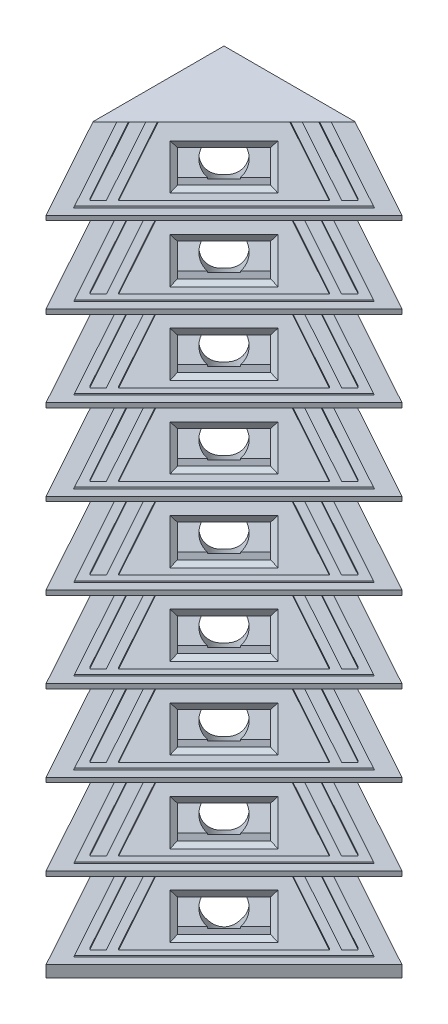
SolidWorks part; units mm, degrees
note: The reader was unsure of these and kept them because the rebuilt part matched: shared geometry of "Sketch6<6>", "Sketch6<8>", "Sketch6<10>".
ref_plane "Front Plane" through (0, 0, 0) normal (0, 0, 1) x (1, 0, 0)
ref_plane "Top Plane" through (0, 0, 0) normal (0, 1, 0) x (1, 0, 0)
ref_plane "Right Plane" through (0, 0, 0) normal (1, 0, 0) x (0, 0, -1)
sketch "Sketch1" plane through (0, 0, 0) normal (0, 1, 0) x (1, 0, 0)
  line L0 (0, 0) -> (0, -34)
  line L1 (0, -55) -> (0, 55) construction
  line L2 (0, -34) -> (34, 0)
  line L3 (-55, 0) -> (55, 0) construction
  line L4 (34, 0) -> (0, 0)
  dimension "D1" = 34
extrude "Boss-Extrude1" add sketch "Sketch1" along normal blind 143
sketch "Sketch3" plane through (17, 0, 17) normal (0.7071, 0, 0.7071) x (0.7071, 0, -0.7071)
  line L0 (-24.0416, 7.9909) -> (24.0416, 7.9909)
  line L1 (-24.0416, 143) -> (-24.0416, 0) construction
  line L2 (24.0416, 143) -> (24.0416, 0) construction
ref_plane "Plane2" through (15.1967, 12.4081, 15.1967) normal (0.6124, 0.5, 0.6124) x (0.7071, 0, -0.7071)
sketch "Sketch6" plane through (15.1967, 12.4081, 15.1967) normal (0.6124, 0.5, 0.6124) x (0.7071, 0, -0.7071)
  line L0 (-24.0416, -5.1005) -> (24.0416, -5.1005)
  line L1 (24.0416, -5.1005) -> (24.0416, 7.5577)
  line L2 (24.0416, 7.5577) -> (-24.0416, 7.5577)
  line L3 (-24.0416, 7.5577) -> (-24.0416, -5.1005)
  line L4 (0, 7.5577) -> (0, -1.1005) construction
  line L5 (-2.2489, -1.1005) -> (-6.3, -1.1005)
  line L6 (-6.3, 3.9995) -> (-2.2489, 3.9995)
  line L7 (-6.3, 3.9995) -> (-6.3, -1.1005)
  line L8 (2.2489, -1.1005) -> (6.3, -1.1005)
  line L9 (6.3, 3.9995) -> (6.3, -1.1005)
  line L10 (-6.3, 3.9995) -> (6.3, -1.1005) construction
  line L11 (-6.3, -1.1005) -> (6.3, 3.9995) construction
  line L13 (-18.1359, -3.1005) -> (-12.8069, 7.5577)
  line L14 (-18.1359, -3.1005) -> (-15.8999, -3.1005)
  line L15 (-20.313, -4.1005) -> (0, -4.1005)
  line L16 (-15.8999, -3.1005) -> (-10.5708, 7.5577)
  line L17 (-8.8937, 7.5577) -> (-14.2228, -3.1005)
  line L18 (-14.2228, -3.1005) -> (0, -3.1005)
  line L19 (-20.313, -4.1005) -> (-14.4839, 7.5577)
  line L20 (0, -3.1005) -> (0, -4.1005)
  line L21 (0, -1.1005) -> (0, -3.1005) construction
  line L22 (0, -1.1005) -> (0, -3.1005) construction
  line L23 (2.2489, 3.9995) -> (6.3, 3.9995)
  line L26 (-2.2489, 3.9995) -> (0, 3.9995)
  line L27 (0, 3.9995) -> (2.2489, 3.9995)
  line L28 (-2.2489, -1.1005) -> (0, -1.1005)
  line L29 (0, -1.1005) -> (2.2489, -1.1005)
  circle A0 centre (0, 1.4495) radius 3.4
  point P4 (0, 1.4495)
  dimension "D9" = 6.8
  dimension "D1" = 12.6
  dimension "D2" = 5.1
  dimension "D3" = 1
  dimension "D5" = 1
  dimension "D6" = 2
  dimension "D7" = 1.5
extrude "Cut-Extrude2" cut sketch "Sketch6" along normal blind 9
extrude "Cut-Extrude3" cut sketch "Sketch6<6>" against normal blind 12.5 and the other way through all contours L9 L6 L7 L8 | L26 A0 L28 L29 L27 | A0 L6 L7 L5
sketch "Sketch6<6>" plane through (15.1967, 12.4081, 15.1967) normal (0.6124, 0.5, 0.6124) x (0.7071, 0, -0.7071) same geometry as "Sketch6"
extrude "Cut-Extrude4" cut sketch "Sketch6<8>" against normal blind 2.5
sketch "Sketch6<8>" plane through (15.1967, 12.4081, 15.1967) normal (0.6124, 0.5, 0.6124) x (0.7071, 0, -0.7071) same geometry as "Sketch6"
ref_plane "Plane3" through (0, 0, 0) normal (-0.7071, 0, 0.7071) x (0.3536, -0.866, 0.3536)
mirror "Mirror1" about plane through (0, 0, 0) normal (-0.7071, 0, 0.7071) of "Cut-Extrude4"
extrude "Cut-Extrude6" cut sketch "Sketch6<10>" against normal blind 20 from offset 10 contours A0 offset against normal yes
sketch "Sketch6<10>" plane through (15.1967, 12.4081, 15.1967) normal (0.6124, 0.5, 0.6124) x (0.7071, 0, -0.7071) same geometry as "Sketch6"
chamfer "Chamfer2" distance 1 angle 45 4 edges at (19.139, 13.6634, 10.2295) (15.5858, 11.455, 15.5858) (10.2295, 13.6634, 19.139) (13.7827, 15.8717, 13.7827)
chamfer "Chamfer1" distance 10 angle 30 1 edges at (17, 0, 17)
pattern_linear "LPattern4" count 9 spacing 15.5 along (0, 1, 0) of "Cut-Extrude2", "Cut-Extrude4", "Cut-Extrude3", "Mirror1", "Chamfer2", "Cut-Extrude6"
